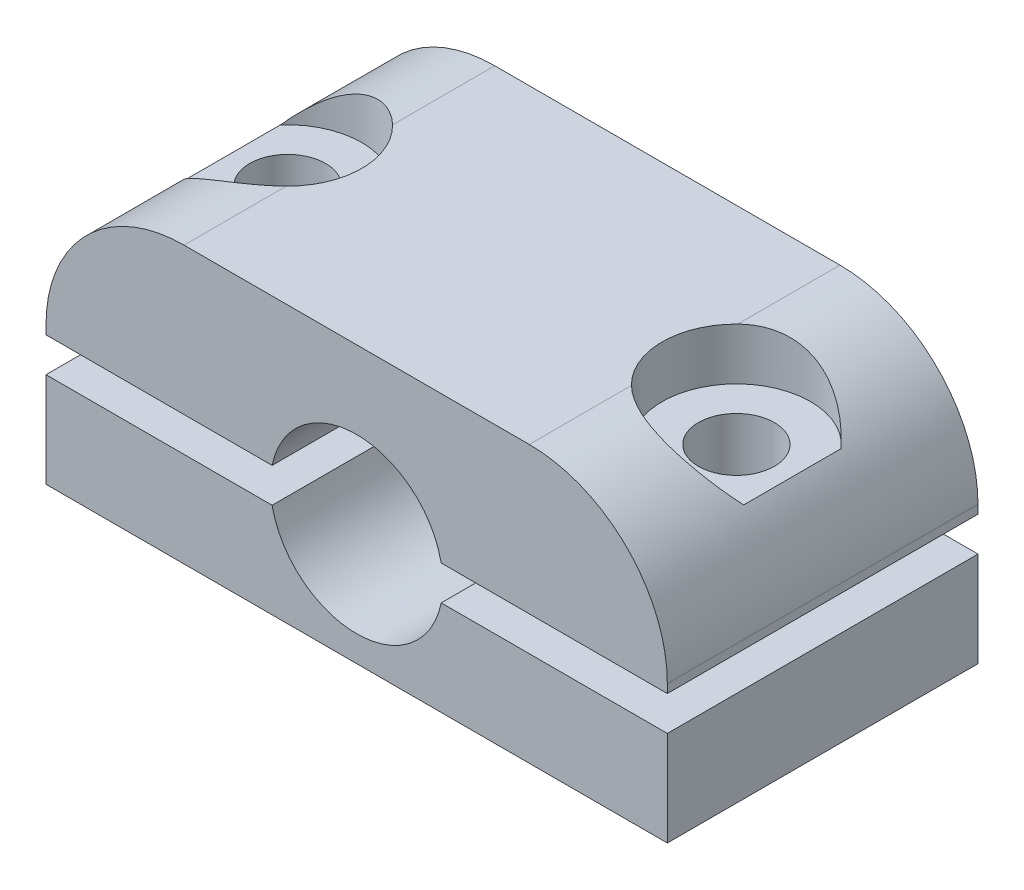
SolidWorks part; units mm, degrees
ref_plane "Спереди" through (0, 0, 0) normal (0, 0, 1) x (1, 0, 0)
ref_plane "Сверху" through (0, 0, 0) normal (0, 1, 0) x (1, 0, 0)
ref_plane "Справа" through (0, 0, 0) normal (1, 0, 0) x (0, 0, -1)
sketch "Эскиз1" plane through (0, 0, 0) normal (0, 1, 0) x (1, 0, 0)
  line L1 (0, 0) -> (36, 0)
  line L2 (0, 0) -> (0, 18)
  line L3 (0, 18) -> (36, 18)
  line L4 (36, 0) -> (36, 18)
  dimension "D1" = 18
  dimension "D2" = 36
extrude "Бобышка-Вытянуть1" add sketch "Эскиз1" along normal blind 16
sketch "Эскиз2" plane through (0, 0, 0) normal (0, -1, 0) x (1, 0, 0)
  line L1 (10, -12) -> (26, -12)
  line L2 (10, -12) -> (10, -6)
  line L3 (10, -6) -> (26, -6)
  line L4 (26, -12) -> (26, -6)
  line L5 (0, -18) -> (0, 0) construction
  line L6 (36, 0) -> (36, -18) construction
  point P4 (10, -9)
  point P5 (0, -9)
  dimension "D1" = 6
  dimension "D3" = 10
  dimension "D4" = 10
extrude "Бобышка-Вытянуть2" add sketch "Эскиз2" along normal blind 3
sketch "Эскиз3" plane through (0, 0, 0) normal (0, -1, 0) x (1, 0, 0)
  line L0 (36, 0) -> (36, -18) construction
  line L1 (0, -18) -> (0, 0) construction
  circle A0 centre (5, -9) radius 2.2
  circle A1 centre (31, -9) radius 2.2
  point P7 (36, -9)
  dimension "D1" = 4.4
  dimension "D2" = 5
  dimension "D3" = 5
extrude "Вырез-Вытянуть1" cut sketch "Эскиз3" against normal blind 30
sketch "Эскиз4" plane through (0, 0, 0) normal (0, 0, 1) x (1, 0, 0)
  line L1 (0, 0) -> (36, 0) construction
  line L2 (37.9488, 7.5) -> (-4.8325, 7.5)
  line L3 (37.9488, 7.5) -> (37.9488, 5.5)
  line L4 (37.9488, 5.5) -> (-4.8325, 5.5)
  line L5 (-4.8325, 7.5) -> (-4.8325, 5.5)
  circle A0 centre (18, 6.5) radius 5
  point P6 (18, 0)
  point P9 (37.9488, 6.5)
  line M4 (36, 0) -> (36, 16)
  line M6 (0, 16) -> (0, 0)
  dimension "D1" = 10
  dimension "D2" = 6.5
  dimension "D3" = 2
extrude "Вырез-Вытянуть2" cut sketch "Эскиз4" against normal blind 30 contours L2 A0 | L2 A0 L4 | L4 A0 | A0 L2 L4 M6 | A0 L4 L2 M4 region at (29.4832, 6.5, 0) region at (18, 6.5, 0) region at (18, 9.1718, 0) region at (6.5168, 6.5, 0) region at (18, 3.8282, 0)
fillet "Скругление1" radius 8 2 edges at (0, 16, -9) (36, 16, -9)
sketch "Эскиз8" plane through (0, 16, 0) normal (0, 1, 0) x (1, 0, 0)
  circle A0 centre (5, 9) radius 4.3
  circle A1 centre (31, 9) radius 4.3
  dimension "D1" = 8.6
  dimension "D2" = 8.6
extrude "Вырез-Вытянуть6" cut sketch "Эскиз8" against normal blind 3
